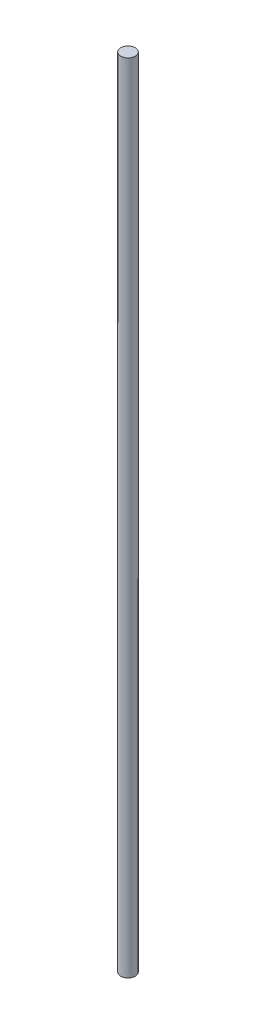
SolidWorks part; units mm, degrees
ref_plane "Front Plane" through (0, 0, 0) normal (0, 0, 1) x (1, 0, 0)
ref_plane "Top Plane" through (0, 0, 0) normal (0, 1, 0) x (1, 0, 0)
ref_plane "Right Plane" through (0, 0, 0) normal (1, 0, 0) x (0, 0, -1)
sketch "Sketch1" plane through (0, 0, 0) normal (0, 1, 0) x (1, 0, 0)
  circle A0 centre (0, 0) radius 2.5
  dimension "D1" = 5
extrude "Boss-Extrude1" add sketch "Sketch1" along normal blind 273.2
